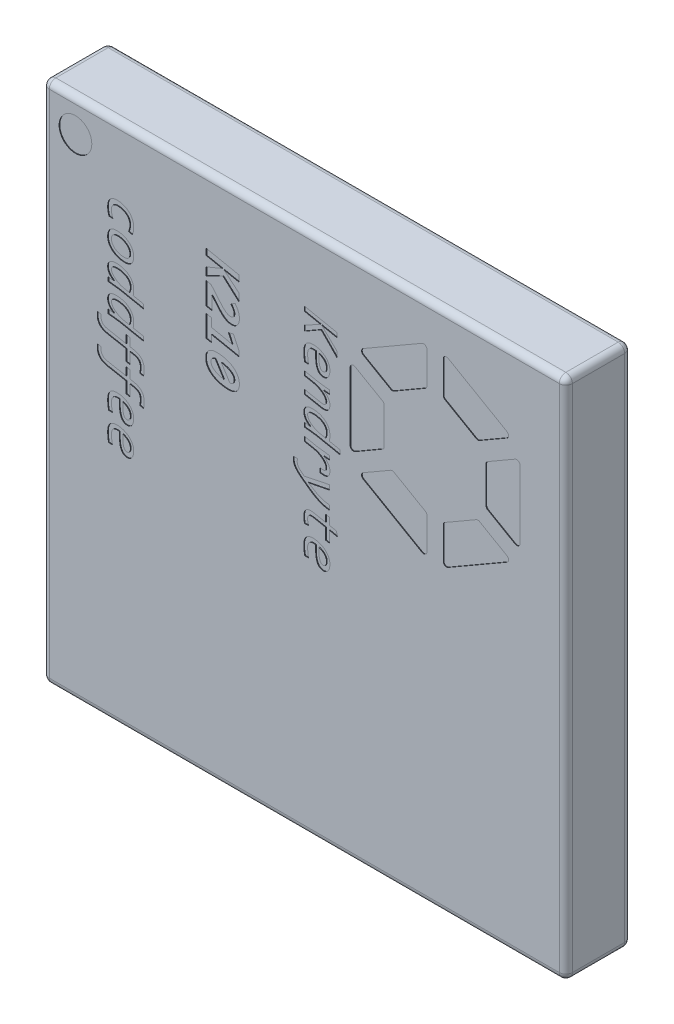
SolidWorks part; units mm, degrees
material "1023 碳钢板 (SS)"
ref_plane "前视基准面" through (0, 0, 0) normal (0, 0, 1) x (1, 0, 0)
ref_plane "上视基准面" through (0, 0, 0) normal (0, 1, 0) x (1, 0, 0)
ref_plane "右视基准面" through (0, 0, 0) normal (1, 0, 0) x (0, 0, -1)
ref_plane "芯片基底面" through (0, 0, 0.15) normal (0, 0, 1) x (1, 0, 0)
sketch "草图1" plane through (0, 0, 0.15) normal (0, 0, 1) x (1, 0, 0)
  line L1 (-4, 4) -> (4, 4)
  line L2 (-4, 4) -> (-4, -4)
  line L3 (-4, -4) -> (4, -4)
  line L4 (4, 4) -> (4, -4)
  line L5 (-4, 4) -> (4, -4) construction
  line L6 (-4, -4) -> (4, 4) construction
  point P0 (0, 0)
extrude "凸台-拉伸1" add sketch "草图1" along normal blind 1
sketch "草图2" plane through (0, 0, 0.15) normal (0, 0, -1) x (-1, 0, 0)
  line L2 (-3.575, 3.725) -> (-3.575, 3.425)
  arc A0 (-3.575, 3.725) -> (-3.575, 3.425) centre (-3.575, 3.575) ccw
revolve "旋转1" add sketch "草图2" angle 180 about L2 reverse direction yes
pattern_linear "阵列(线性)1" count 12 spacing 0.65 along (-1, 0, 0) of "旋转1"
pattern_linear "阵列(线性)2" count 12 spacing 0.65 along (0, -1, 0) of "旋转1", "阵列(线性)1"
sketch "草图3" plane through (0, 0, 1.15) normal (0, 0, 1) x (1, 0, 0)
  line L1 (0, 3) -> (0, -3) construction
  line L41 (3.299, 2.5191) -> (3.299, 1.4809)
  line L42 (3.224, 1.4376) -> (2.8044, 1.6799)
  line L43 (2.7794, 2.2768) -> (2.7794, 1.7232)
  line L44 (3.224, 2.5624) -> (2.8044, 2.3201)
  line L45 (3.099, 1.1345) -> (2.2, 0.6155)
  line L46 (2.125, 0.6588) -> (2.125, 1.1433)
  line L47 (2.6294, 1.4634) -> (2.15, 1.1866)
  line L48 (3.099, 1.2211) -> (2.6794, 1.4634)
  line L49 (1.8, 0.6155) -> (0.901, 1.1345)
  line L50 (0.901, 1.2211) -> (1.3206, 1.4634)
  line L51 (1.85, 1.1866) -> (1.3706, 1.4634)
  line L52 (1.875, 0.6588) -> (1.875, 1.1433)
  line L53 (0.701, 1.4809) -> (0.701, 2.5191)
  line L54 (0.776, 2.5624) -> (1.1956, 2.3201)
  line L55 (1.2206, 1.7232) -> (1.2206, 2.2768)
  line L56 (0.776, 1.4376) -> (1.1956, 1.6799)
  line L57 (0.901, 2.8655) -> (1.8, 3.3845)
  line L58 (1.875, 3.3412) -> (1.875, 2.8567)
  line L59 (1.3706, 2.5366) -> (1.85, 2.8134)
  line L60 (0.901, 2.7789) -> (1.3206, 2.5366)
  line L61 (2.125, 3.3412) -> (2.125, 2.8567)
  line L62 (2.2, 3.3845) -> (3.099, 2.8655)
  line L63 (2.15, 2.8134) -> (2.6294, 2.5366)
  line L64 (3.099, 2.7789) -> (2.6794, 2.5366)
  line L67 (-1.5, 3) -> (-1.5, 0) construction
  line L68 (-3, 3) -> (-3, -3) construction
  arc A30 (3.224, 1.4376) -> (3.299, 1.4809) centre (3.249, 1.4809) ccw
  arc A31 (2.7794, 1.7232) -> (2.8044, 1.6799) centre (2.8294, 1.7232) ccw
  arc A32 (2.8044, 2.3201) -> (2.7794, 2.2768) centre (2.8294, 2.2768) ccw
  arc A33 (3.224, 2.5624) -> (3.299, 2.5191) centre (3.249, 2.5191) cw
  arc A34 (2.125, 0.6588) -> (2.2, 0.6155) centre (2.175, 0.6588) ccw
  arc A35 (2.15, 1.1866) -> (2.125, 1.1433) centre (2.175, 1.1433) ccw
  arc A36 (2.6794, 1.4634) -> (2.6294, 1.4634) centre (2.6544, 1.4201) ccw
  arc A37 (3.099, 1.2211) -> (3.099, 1.1345) centre (3.074, 1.1778) cw
  arc A38 (0.901, 1.2211) -> (0.901, 1.1345) centre (0.926, 1.1778) ccw
  arc A39 (1.3706, 1.4634) -> (1.3206, 1.4634) centre (1.3456, 1.4201) ccw
  arc A40 (1.875, 1.1433) -> (1.85, 1.1866) centre (1.825, 1.1433) ccw
  arc A41 (1.875, 0.6588) -> (1.8, 0.6155) centre (1.825, 0.6588) cw
  arc A42 (0.776, 2.5624) -> (0.701, 2.5191) centre (0.751, 2.5191) ccw
  arc A43 (1.2206, 2.2768) -> (1.1956, 2.3201) centre (1.1706, 2.2768) ccw
  arc A44 (1.1956, 1.6799) -> (1.2206, 1.7232) centre (1.1706, 1.7232) ccw
  arc A45 (0.776, 1.4376) -> (0.701, 1.4809) centre (0.751, 1.4809) cw
  arc A46 (1.875, 3.3412) -> (1.8, 3.3845) centre (1.825, 3.3412) ccw
  arc A47 (1.85, 2.8134) -> (1.875, 2.8567) centre (1.825, 2.8567) ccw
  arc A48 (1.3206, 2.5366) -> (1.3706, 2.5366) centre (1.3456, 2.5799) ccw
  arc A49 (0.901, 2.7789) -> (0.901, 2.8655) centre (0.926, 2.8222) cw
  arc A50 (2.125, 3.3412) -> (2.2, 3.3845) centre (2.175, 3.3412) cw
  arc A51 (3.099, 2.7789) -> (3.099, 2.8655) centre (3.074, 2.8222) ccw
  arc A52 (2.6294, 2.5366) -> (2.6794, 2.5366) centre (2.6544, 2.5799) ccw
  arc A53 (2.125, 2.8567) -> (2.15, 2.8134) centre (2.175, 2.8567) ccw
  circle A54 centre (-3.5, 3.5) radius 0.25
  text T0 "<i>Kendryte</i>" font "Consolas" height 0.5
  text T1 "<b><i>K210</i></b>" font "Consolas" height 0.5
  text T2 "<i>coddffee</i>" font "Consolas" height 0.5
  point P3 (0, 0)
  point P151 (2, 2)
extrude "切除-拉伸1" cut sketch "草图3" against normal blind 0.01
fillet "圆角1" radius 0.1 4 edges at (4, 4, 0.65) (4, -4, 0.65) (-4, -4, 0.65) (-4, 4, 0.65)
fillet "圆角2" radius 0.1 16 edges at (-3.9707, -3.9707, 0.15) (-4, 0, 0.15) (-3.9707, 3.9707, 0.15) (0, 4, 0.15) (3.9707, 3.9707, 0.15) (4, 0, 0.15) (3.9707, -3.9707, 0.15) (-3.9707, -3.9707, 1.15) (-4, 0, 1.15) (-3.9707, 3.9707, 1.15) (0, 4, 1.15) (3.9707, 3.9707, 1.15) (4, 0, 1.15) (3.9707, -3.9707, 1.15) (0, -4, 0.15) (0, -4, 1.15)
